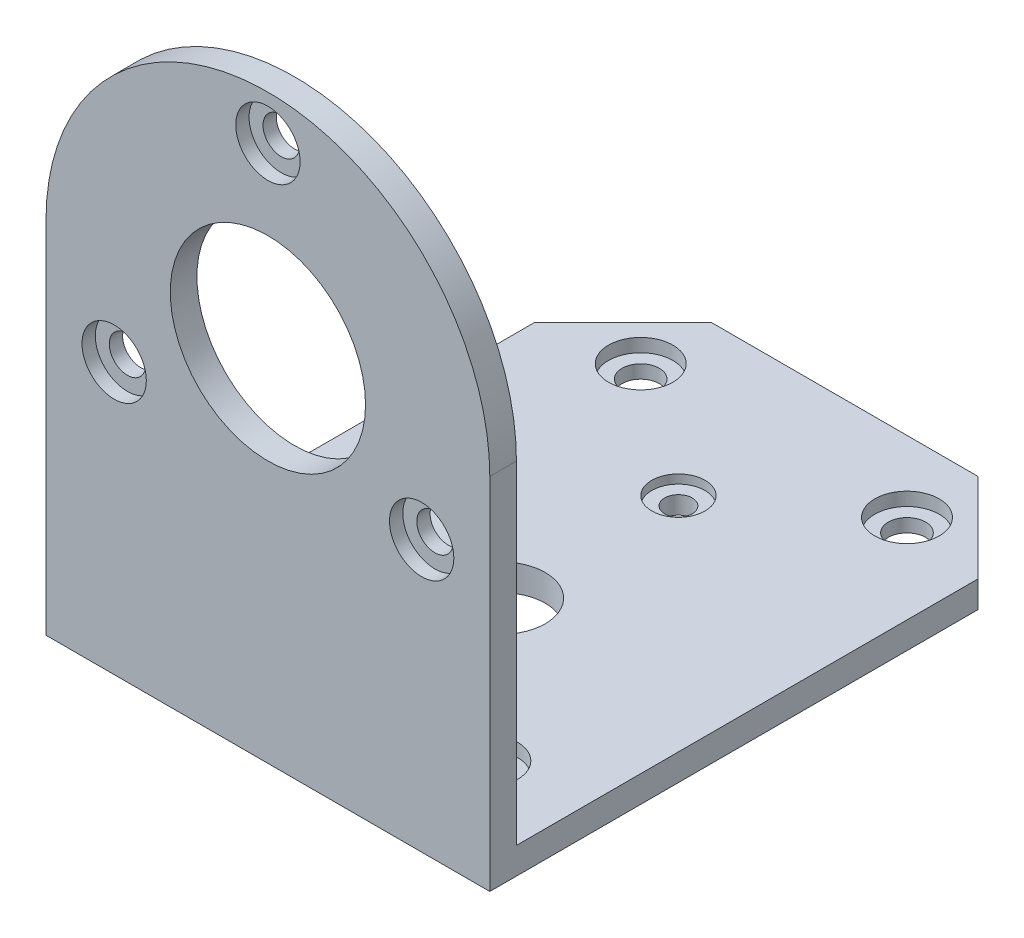
SolidWorks part; units mm, degrees
material "Nylon 101"
ref_plane "前视基准面" through (0, 0, 0) normal (0, 0, 1) x (1, 0, 0)
ref_plane "上视基准面" through (0, 0, 0) normal (0, 1, 0) x (1, 0, 0)
ref_plane "右视基准面" through (0, 0, 0) normal (1, 0, 0) x (0, 0, -1)
sketch "草图1" plane through (0, 0, 0) normal (0, 0, 1) x (1, 0, 0)
  line L0 (0, 0) -> (0, 90) construction
  circle A0 centre (0, 90) radius 11
  arc A2 (19, 72) -> (20, 75) centre (24, 72) cw
  circle A3 centre (0, 90) radius 25
  arc A5 (-19, 72) -> (-20, 75) centre (-24, 72) ccw
  circle A6 centre (0, 110) radius 2.05
  circle A7 centre (17.3205, 80) radius 2.05
  circle A8 centre (-17.3205, 80) radius 2.05
  point P30 (0, 90)
  dimension "D4" = 50
  dimension "D8" = 4.1
  dimension "D2" = 22
  dimension "D10" = 20
  dimension "D12" = 5
  dimension "D9" = 40
  dimension "D11" = 3
extrude "凸台-拉伸1" add sketch "草图1" along normal mid plane 3 contours A3 | L0 A3 A5 | L0 A2 A3 | L0 | L0 region at (23.0463, 82.3179, 0)
sketch "草图3" plane through (0, 0, -1.5) normal (0, 0, -1) x (-1, 0, 0)
  line L0 (-25, 90) -> (-25, 52.5)
  line L1 (-25, 52.5) -> (25, 52.5)
  line L2 (25, 52.5) -> (25, 90)
  circle A0 centre (0, 90) radius 25 construction
  circle A1 centre (0, 90) radius 25 construction
  circle A2 centre (0, 90) radius 25
  circle M5 centre (0, 90) radius 25
  dimension "D1" = 37.5
extrude "凸台-拉伸2" add sketch "草图3" against normal up to surface (3 mm away) contours L0 L1 M5 | L1 L2 M5 region at (0, 62.3039, -1.5) up to face at (11, 90, 1.5)
sketch "草图4" plane through (0, 0, 1.5) normal (0, 0, 1) x (1, 0, 0)
  line L0 (25, 52.5) -> (25, 49.5)
  line L1 (25, 49.5) -> (-25, 49.5)
  line L2 (-25, 52.5) -> (-25, 49.5)
  line L3 (25, 52.5) -> (-25, 52.5) construction
  line L4 (25, 52.5) -> (-25, 52.5)
  dimension "D1" = 3
extrude "凸台-拉伸3" add sketch "草图4" against normal blind 65
sketch "草图6" plane through (0, 52.5, 0) normal (0, 1, 0) x (1, 0, 0)
  line L0 (-15, 63.5) -> (-25, 53.5)
  line L1 (25, 53.5) -> (15, 63.5)
  line L4 (-25, 1.5) -> (25, 1.5)
  line L5 (25, 1.5) -> (25, 63.5)
  line L6 (25, 63.5) -> (-25, 63.5)
  line L7 (-25, 63.5) -> (-25, 1.5)
  line L8 (-25, 1.5) -> (25, 1.5)
  line L9 (25, 1.5) -> (25, 53.5)
  line L10 (15, 63.5) -> (-15, 63.5)
  line L11 (-25, 53.5) -> (-25, 1.5)
  line M8 (25, 1.5) -> (25, 63.5)
  line M9 (25, 63.5) -> (-25, 63.5)
  line M10 (-25, 63.5) -> (-25, 1.5)
  dimension "D1" = 0
extrude "切除-拉伸1" cut sketch "草图6" against normal blind 55 contours L0 M9 M10 | L1 M8 M9 region at (-21.6667, 52.5, -60.1667) region at (21.6667, 52.5, -60.1667)
sketch "草图7" plane through (0, 52.5, 0) normal (0, 1, 0) x (1, 0, 0)
  line L0 (0, 0) -> (0, 63.5) construction
  line L1 (15, 63.5) -> (-15, 63.5) construction
  line L2 (-25, 53.5) -> (-25, 1.5) construction
  line L3 (-15, 55.5) -> (15, 55.5) construction
  line L4 (-15, 55.5) -> (-15, 8) construction
  line L5 (-15, 8) -> (15, 8) construction
  line L6 (15, 55.5) -> (15, 8) construction
  line L7 (-15, 55.5) -> (15, 8) construction
  line L8 (-15, 8) -> (15, 55.5) construction
  circle A0 centre (-15, 55.5) radius 2.1
  circle A1 centre (15, 55.5) radius 2.1
  circle A2 centre (15, 8) radius 2.1
  circle A3 centre (-15, 8) radius 2.1
  point P5 (0, 31.75)
  dimension "D3" = 4.2
  dimension "D4" = 4.2
  dimension "D5" = 4.2
  dimension "D6" = 4.2
  dimension "D1" = 8
  dimension "D2" = 10
  dimension "D7" = 47.5
  dimension "D8" = 30
extrude "切除-拉伸2" cut sketch "草图7" against normal blind 55
sketch "草图9" plane through (0, 52.5, 0) normal (0, 1, 0) x (1, 0, 0)
  circle A0 centre (-15, 55.5) radius 3.625
  circle A1 centre (15, 55.5) radius 3.625
  circle A2 centre (15, 8) radius 3.625
  circle A3 centre (-15, 8) radius 3.625
  dimension "D1" = 7.25
  dimension "D2" = 7.25
  dimension "D3" = 7.25
  dimension "D4" = 7.25
extrude "切除-拉伸3" cut sketch "草图9" against normal blind 1.5
sketch "草图10" plane through (0, 52.5, 0) normal (0, 1, 0) x (1, 0, 0)
  line L0 (-25, 24.75) -> (25, 24.75) construction
  line L1 (-25, 53.5) -> (-25, 1.5) construction
  line L2 (25, 53.5) -> (25, 1.5) construction
  line L3 (25, 1.5) -> (-25, 1.5) construction
  line L4 (0, 24.75) -> (0, 50.696) construction
  dimension "D1" = 23.25
sketch "草图11" plane through (0, 0, 1.5) normal (0, 0, 1) x (1, 0, 0)
  circle A0 centre (0, 110) radius 2.05 construction
  circle A1 centre (0, 110) radius 2.05
  circle A2 centre (-17.3205, 80) radius 2.05 construction
  circle A3 centre (-17.3205, 80) radius 2.05
  circle A4 centre (17.3205, 80) radius 2.05 construction
  circle A5 centre (17.3205, 80) radius 2.05
  circle A6 centre (0, 110) radius 3.625
  circle A7 centre (17.3205, 80) radius 3.625
  circle A8 centre (-17.3205, 80) radius 3.625
  dimension "D1" = 7.25
  dimension "D2" = 7.25
  dimension "D3" = 7.25
extrude "切除-拉伸4" cut sketch "草图11" against normal blind 1.5
sketch "草图12" plane through (0, 49.5, 0) normal (0, -1, 0) x (1, 0, 0)
  circle A0 centre (0, -4.75) radius 1.55 construction
  circle A1 centre (0, -4.75) radius 1.55
  circle A2 centre (0, -44.75) radius 1.55 construction
  circle A3 centre (0, -44.75) radius 1.55
  circle A4 centre (0, -24.75) radius 5 construction
  circle A5 centre (0, -24.75) radius 5
extrude "切除-拉伸5" cut sketch "草图12" against normal blind 6.5
sketch "草图13" plane through (0, 52.5, 0) normal (0, 1, 0) x (1, 0, 0)
  circle A0 centre (0, 44.75) radius 3
  circle A1 centre (0, 4.75) radius 3
  circle M1 centre (0, 4.75) radius 1.55
  circle M2 centre (0, 44.75) radius 1.55
  dimension "D1" = 6
  dimension "D2" = 6
extrude "切除-拉伸13" cut sketch "草图13" against normal offset from surface (1 mm away) 2 contours A1 M1 | A0 M2 region at (-2.9151, 52.5, -44.75) region at (-2.9151, 52.5, -4.75) up to face at (1.55, 49.5, -4.75)
